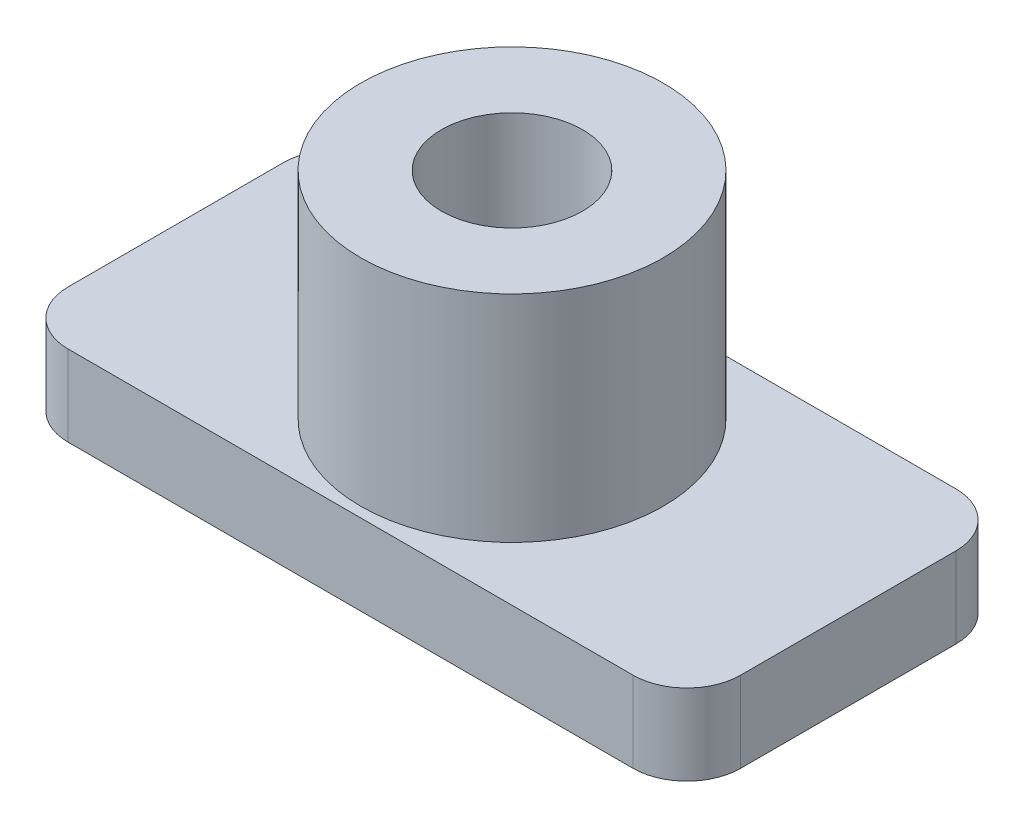
SolidWorks part; units mm, degrees
ref_plane "Front Plane" through (0, 0, 0) normal (0, 0, 1) x (1, 0, 0)
ref_plane "Top Plane" through (0, 0, 0) normal (0, 1, 0) x (1, 0, 0)
ref_plane "Right Plane" through (0, 0, 0) normal (1, 0, 0) x (0, 0, -1)
sketch "Sketch1" plane through (0, 0, 0) normal (0, 1, 0) x (1, 0, 0)
  line L1 (12.5, -6) -> (-12.5, -6)
  line L2 (12.5, -6) -> (12.5, 6)
  line L3 (12.5, 6) -> (-12.5, 6)
  line L4 (-12.5, -6) -> (-12.5, 6)
  line L5 (12.5, -6) -> (-12.5, 6) construction
  line L6 (12.5, 6) -> (-12.5, -6) construction
  point P0 (0, 0)
  dimension "D1" = 25
  dimension "D2" = 12
extrude "Boss-Extrude1" add sketch "Sketch1" along normal blind 3
sketch "Sketch2" plane through (0, 3, 0) normal (0, 1, 0) x (1, 0, 0)
  circle A0 centre (0, 0) radius 5.625
  circle A1 centre (0, 0) radius 2.625
  dimension "D1" = 3
  dimension "D2" = 5.25
extrude "Boss-Extrude2" add sketch "Sketch2" along normal blind 8
fillet "Fillet1" radius 2 4 edges at (12.5, 1.5, -6) (12.5, 1.5, 6) (-12.5, 1.5, -6) (-12.5, 1.5, 6)
